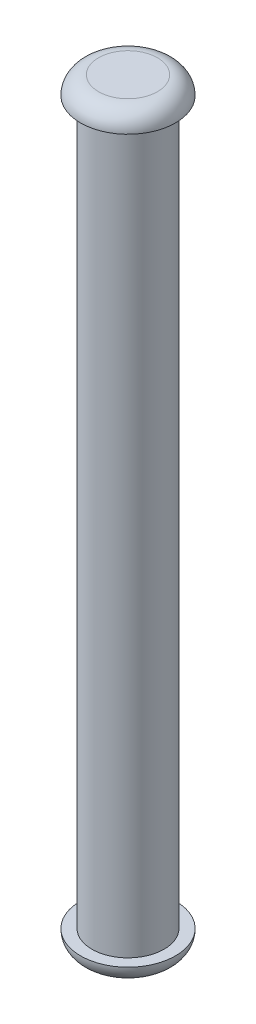
SolidWorks part; units mm, degrees
material "Cast Carbon Steel"
ref_plane "Front Plane" through (0, 0, 0) normal (0, 0, 1) x (1, 0, 0)
ref_plane "Top Plane" through (0, 0, 0) normal (0, 1, 0) x (1, 0, 0)
ref_plane "Right Plane" through (0, 0, 0) normal (1, 0, 0) x (0, 0, -1)
sketch "Sketch1" plane through (0, 0, 0) normal (0, 1, 0) x (1, 0, 0)
  circle A0 centre (0, 0) radius 2
extrude "Boss-Extrude1" add sketch "Sketch1" along normal blind 40
sketch "Sketch2" plane through (0, 40, 0) normal (0, 1, 0) x (1, 0, 0)
  circle A0 centre (0, 0) radius 2.6331
extrude "Boss-Extrude2" add sketch "Sketch2" along normal blind 1
fillet "Fillet1" radius 1
sketch "Sketch3" plane through (0, 0, 0) normal (0, -1, 0) x (1, 0, 0)
  circle A1 centre (0, 0) radius 2.6331
  circle A2 centre (0, 0) radius 2.6331
  dimension "D1" = 0
extrude "Boss-Extrude3" add sketch "Sketch3" along normal blind 1
fillet "Fillet2" radius 1
